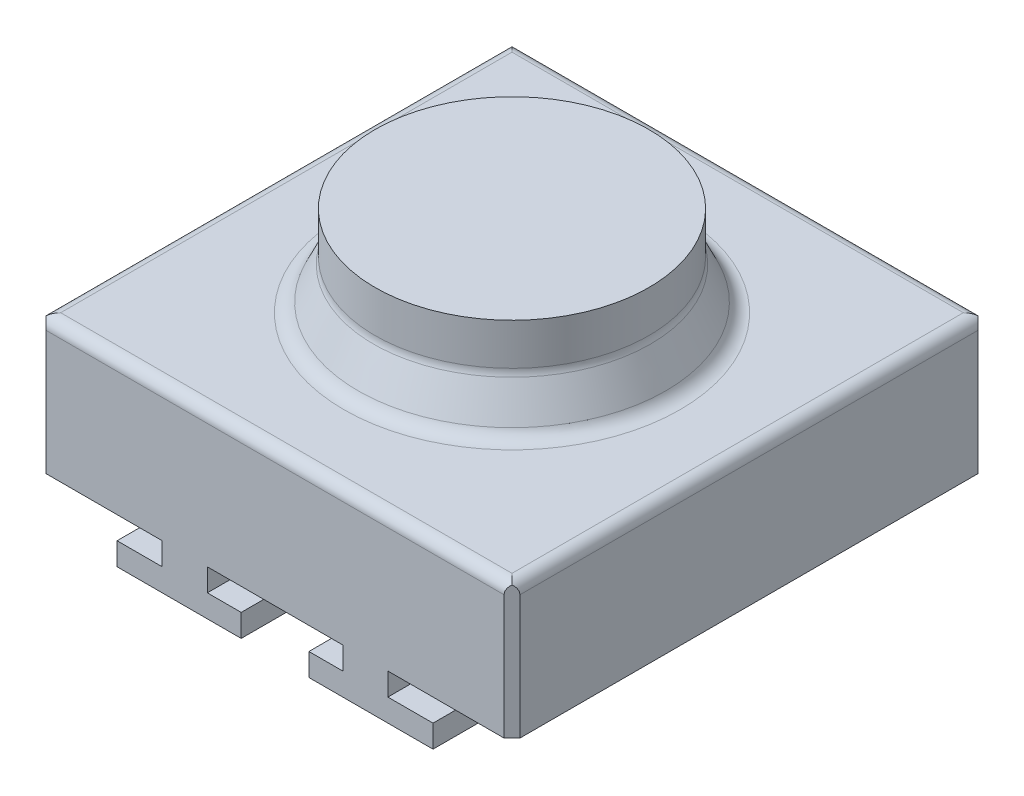
SolidWorks part; units mm, degrees
ref_plane "Front Plane" through (0, 0, 0) normal (0, 0, 1) x (1, 0, 0)
ref_plane "Top Plane" through (0, 0, 0) normal (0, 1, 0) x (1, 0, 0)
ref_plane "Right Plane" through (0, 0, 0) normal (1, 0, 0) x (0, 0, -1)
sketch "Sketch2" plane through (0, 0, 0) normal (0, 0, 1) x (1, 0, 0)
  line L0 (0, 0) -> (55, 0)
  line L1 (55, 0) -> (55, 10)
  line L2 (55, 10) -> (40, 10)
  line L3 (40, 10) -> (40, 20)
  line L5 (20, 20) -> (20, 10)
  line L6 (20, 10) -> (0, 10)
  line L7 (0, 10) -> (0, 0)
  line L8 (20, 20) -> (-35, 20)
  line L9 (-35, 20) -> (-35, 80)
  line L10 (-35, 80) -> (175, 80)
  line L11 (175, 80) -> (175, 20)
  line L12 (175, 20) -> (120, 20)
  line L13 (120, 20) -> (120, 10)
  line L14 (120, 10) -> (140, 10)
  line L15 (140, 10) -> (140, 0)
  line L16 (140, 0) -> (85, 0)
  line L17 (85, 0) -> (85, 10)
  line L18 (85, 10) -> (100, 10)
  line L19 (100, 10) -> (100, 20)
  line L20 (100, 20) -> (40, 20)
  line L21 (27.5, 0) -> (27.5, 84.9327) construction
  line L22 (112.5, 0) -> (112.5, 107.9904) construction
  line L23 (70, 80) -> (70, -28.1594) construction
  dimension "D2" = 10
  dimension "D3" = 210
  dimension "D4" = 20
  dimension "D5" = 15
  dimension "D6" = 20
  dimension "D7" = 20
  dimension "D8" = 140
  dimension "D9" = 15
  dimension "D10" = 10
  dimension "D11" = 60
  dimension "D12" = 20
extrude "Boss-Extrude1" add sketch "Sketch2" along normal blind 210
sketch "Sketch3" plane through (0, 80, 0) normal (0, 1, 0) x (1, 0, 0)
  line L0 (70, 0) -> (70, -105) construction
  line L1 (175, 0) -> (-35, 0) construction
  line L2 (-35, -105) -> (70, -105) construction
  line L3 (-35, -210) -> (-35, 0) construction
  circle A0 centre (70, -105) radius 70
  dimension "D1" = 140
extrude "Boss-Extrude2" add sketch "Sketch3" along normal blind 20 draft 25
sketch "Sketch4" plane through (0, 100, 0) normal (0, 1, 0) x (1, 0, 0)
  circle A0 centre (70, -105) radius 60.6738
  circle A1 centre (70, -105) radius 60.6738 construction
extrude "Boss-Extrude3" add sketch "Sketch4" along normal blind 20
chamfer "Chamfer1" distance 3.5 angle 45 4 edges at (-35, 50, 0) (175, 50, 0) (-35, 50, 210) (175, 50, 210)
fillet "Fillet1" radius 7 2 edges at (9.3262, 100, 105) (0, 80, 105)
fillet "Fillet2" radius 5 4 edges at (-35, 80, 105) (70, 80, 0) (175, 80, 105) (70, 80, 210)
